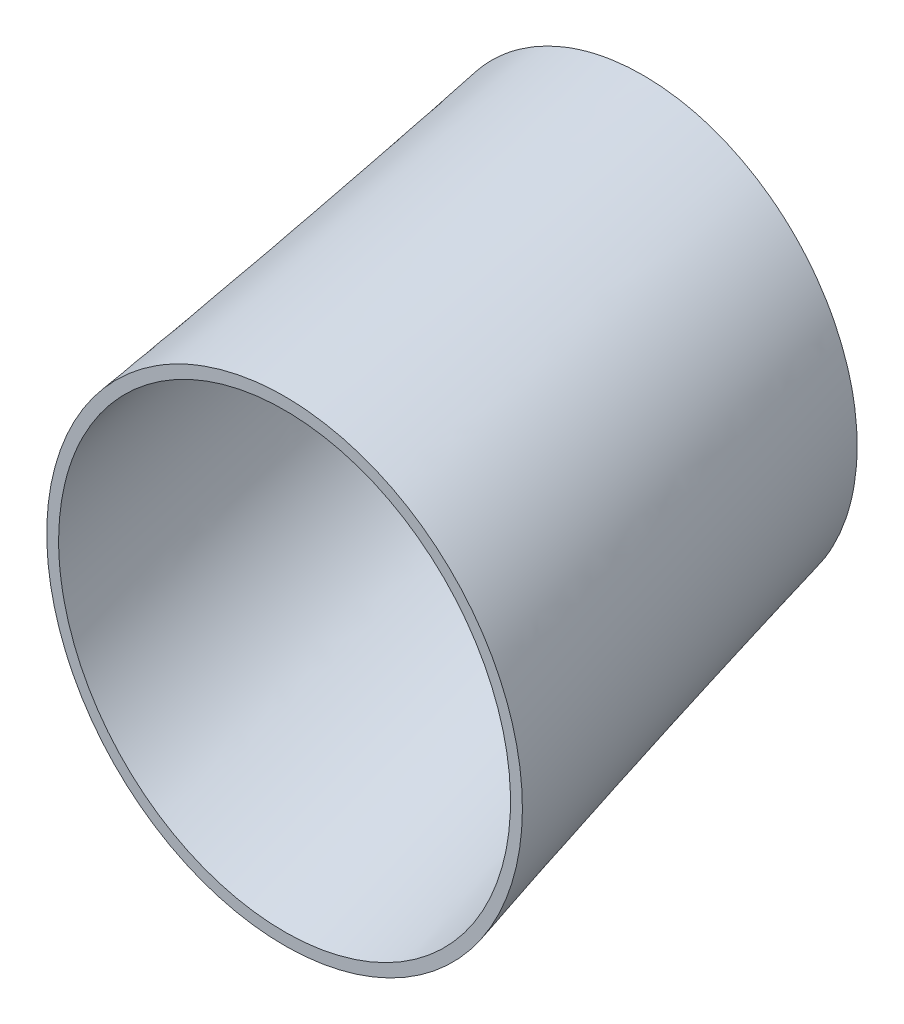
SolidWorks part; units mm, degrees
ref_plane "Front Plane" through (0, 0, 0) normal (0, 0, 1) x (1, 0, 0)
ref_plane "Top Plane" through (0, 0, 0) normal (0, 1, 0) x (1, 0, 0)
ref_plane "Right Plane" through (0, 0, 0) normal (1, 0, 0) x (0, 0, -1)
sketch "Sketch1" plane through (0, 0, 0) normal (0, 0, 1) x (1, 0, 0)
  circle A0 centre (0, 28.1706) radius 9 construction
  circle A1 centre (0, 28.1706) radius 9
sketch "Sketch2" plane through (0, 0, 15.5748) normal (0, 0, -1) x (-1, 0, 0)
  circle A0 centre (-0.5, 23.5133) radius 10 construction
  circle A1 centre (-0.5, 23.5133) radius 10
loft "Loft1" add profiles "Sketch2", "Sketch1" connector at (2.8283, 13.7881, 15.5748) connector at (-0.0792, 19.171, 0)
sketch "Sketch3" plane through (0, 0, 15.5748) normal (0, 0, 1) x (1, 0, 0)
  circle A2 centre (0.5, 23.5133) radius 9.5
  circle A3 centre (0.5, 23.5133) radius 9.5
  dimension "D1" = 0.5
sketch "Sketch4" plane through (0, 0, 0) normal (0, 0, -1) x (-1, 0, 0)
  circle A2 centre (0, 28.1706) radius 8.5
  circle A3 centre (0, 28.1706) radius 8.5
  dimension "D1" = 0.5
loft "Cut-Loft1" cut profiles "Sketch4", "Sketch3" connector at (8.3622, 26.6461, 0) connector at (9.9297, 22.3595, 15.5748)
